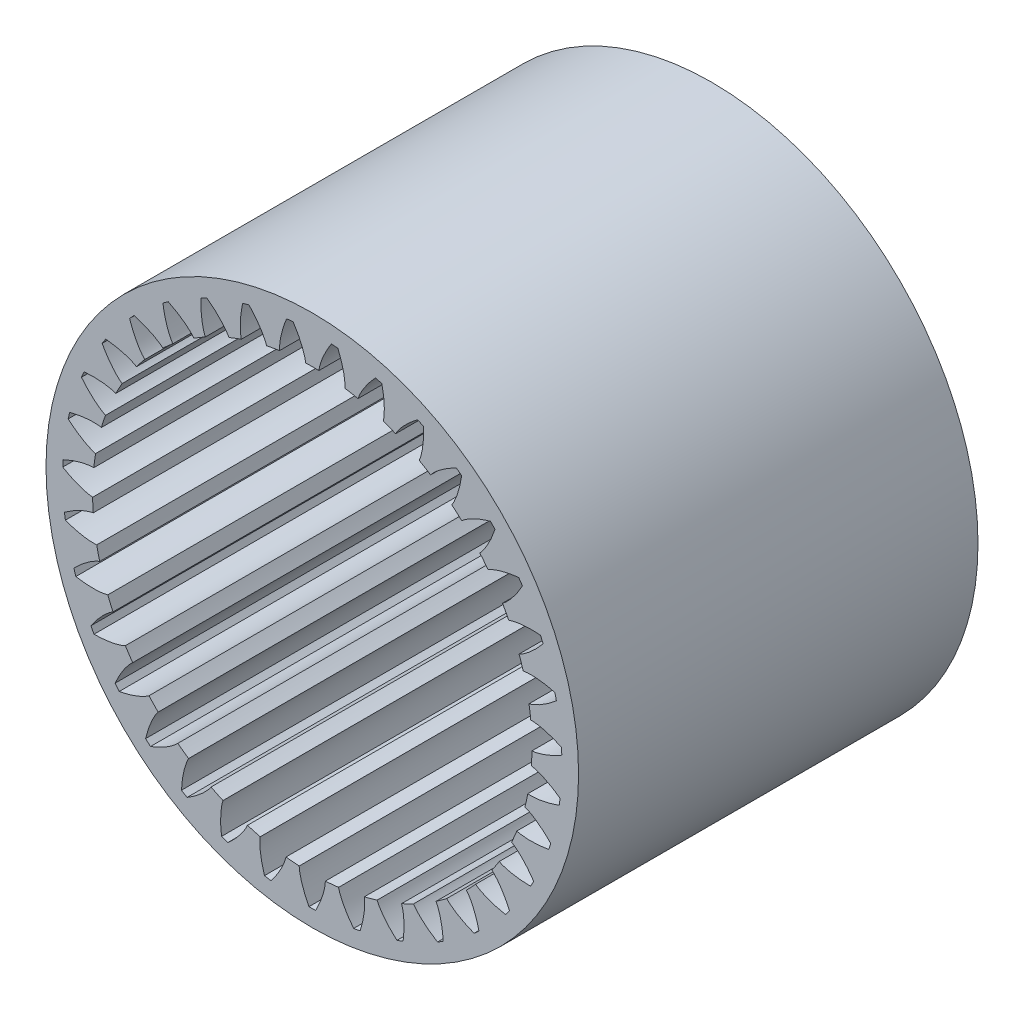
SolidWorks part; units mm, degrees
ref_plane "前视基准面" through (0, 0, 0) normal (0, 0, 1) x (1, 0, 0)
ref_plane "上视基准面" through (0, 0, 0) normal (0, 1, 0) x (1, 0, 0)
ref_plane "右视基准面" through (0, 0, 0) normal (1, 0, 0) x (0, 0, -1)
sketch "草图1" plane through (0, 0, 0) normal (0, 0, 1) x (1, 0, 0)
  circle A0 centre (0, 0) radius 18.75
  circle A1 centre (0, 0) radius 21
extrude "凸台-拉伸1" add sketch "草图1" along normal blind 30
ref_axis "基准轴1" through (0, 0, -1.5) along (0, 0, 1)
sketch "草图2" plane through (0, 0, 0) normal (0, 0, 1) x (1, 0, 0)
  line L0 (0, 0) -> (0, 16.5) construction
  arc A0 (0.4975, 16.4922) -> (-0.4975, 16.4922) centre (0, 0) ccw
  arc A1 (1.6131, 18.9581) -> (-1.6131, 18.9581) centre (0, 0) ccw
  spline S0 degree 3 poles (0.4975, 16.4922) (0.5017, 16.5288) (0.5096, 16.5817) (0.5227, 16.6529) (0.5341, 16.7083) (0.548, 16.7699) (0.5648, 16.8375) (0.5846, 16.9112) (0.6077, 16.9908) (0.6343, 17.0762) (0.6647, 17.1673) (0.6991, 17.2639) (0.7378, 17.366) (0.781, 17.4734) (0.8289, 17.586) (0.8817, 17.7036) (0.9397, 17.8261) (1.003, 17.9532) (1.072, 18.0849) (1.1467, 18.221) (1.2274, 18.3613) (1.3143, 18.5055) (1.4409, 18.7066) (1.5423, 18.8572) (1.6131, 18.9581) knots 0 0 0 0 0.04047 0.05878 0.0795 0.10263 0.12817 0.156121 0.186481 0.219251 0.254431 0.292021 0.332021 0.374431 0.419251 0.466481 0.516121 0.568171 0.622631 0.679501 0.738781 0.800471 0.86457 1 1 1 1
  spline S1 degree 3 poles (-0.4975, 16.4922) (-0.5017, 16.5288) (-0.5096, 16.5817) (-0.5227, 16.6529) (-0.5341, 16.7083) (-0.548, 16.7699) (-0.5648, 16.8375) (-0.5846, 16.9112) (-0.6077, 16.9908) (-0.6343, 17.0762) (-0.6647, 17.1673) (-0.6991, 17.2639) (-0.7378, 17.366) (-0.781, 17.4734) (-0.8289, 17.586) (-0.8817, 17.7036) (-0.9397, 17.8261) (-1.003, 17.9532) (-1.072, 18.0849) (-1.1467, 18.221) (-1.2274, 18.3613) (-1.3143, 18.5055) (-1.4409, 18.7066) (-1.5423, 18.8572) (-1.6131, 18.9581) knots 0 0 0 0 0.04047 0.05878 0.0795 0.10263 0.12817 0.156121 0.186481 0.219251 0.254431 0.292021 0.332021 0.374431 0.419251 0.466481 0.516121 0.568171 0.622631 0.679501 0.738781 0.800471 0.86457 1 1 1 1
extrude "凸台-拉伸2" add sketch "草图2" along normal blind 30
pattern_circular "阵列(圆周)1" count 35 every 10.286 about axis through (0, 0, -1.5) along (0, 0, 1) of "凸台-拉伸2"
sketch "草图3" plane through (0, 0, 0) normal (0, 0, 1) x (1, 0, 0)
  circle A0 centre (0, 0) radius 17.5 construction
  dimension "Dn" = 35
sketch "草图4" plane through (0, 0, 30) normal (0, 0, 1) x (1, 0, 0)
  circle A0 centre (0, 0) radius 20
  circle A1 centre (0, 0) radius 21
  dimension "D1" = 40
extrude "切除-拉伸1" cut sketch "草图4" against normal blind 115
